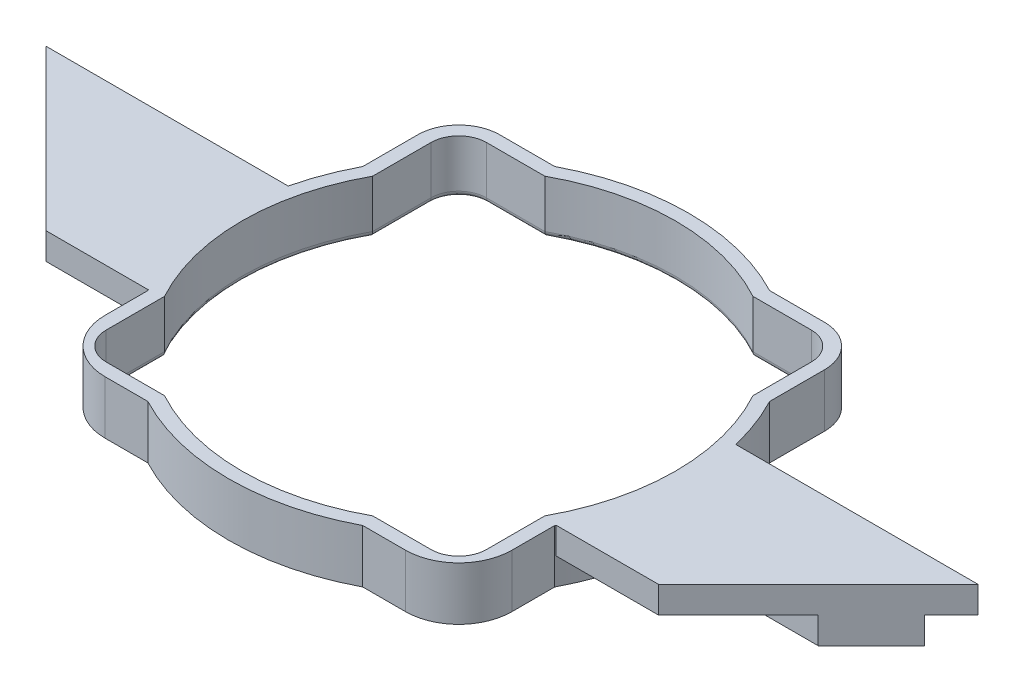
SolidWorks part; units mm, degrees
ref_plane "Front Plane" through (0, 0, 0) normal (0, 0, 1) x (1, 0, 0)
ref_plane "Top Plane" through (0, 0, 0) normal (0, 1, 0) x (1, 0, 0)
ref_plane "Right Plane" through (0, 0, 0) normal (1, 0, 0) x (0, 0, -1)
sketch "Sketch1" plane through (0, 0, 0) normal (0, 1, 0) x (1, 0, 0)
  line L1 (-127, -76.2) -> (127, -76.2)
  line L2 (-127, -76.2) -> (-127, 76.2)
  line L3 (-127, 76.2) -> (127, 76.2)
  line L4 (127, -76.2) -> (127, 76.2)
  line L5 (-127, -76.2) -> (127, 76.2) construction
  line L6 (-127, 76.2) -> (127, -76.2) construction
  point P0 (0, 0)
  dimension "D1" = 254
  dimension "D2" = 152.4
extrude "Boss-Extrude1" add sketch "Sketch1" along normal blind 12.7 contours L2 L3 L4 L1
sketch "Sketch4" plane through (0, 0, 0) normal (0, -1, 0) x (1, 0, 0)
  line L0 (45.339, 24.8219) -> (45.339, 38.735)
  line L1 (38.735, 45.339) -> (24.8219, 45.339)
  line L2 (-24.8219, 45.339) -> (-38.735, 45.339)
  line L3 (-45.339, 38.735) -> (-45.339, 24.8219)
  line L4 (-45.339, -24.8219) -> (-45.339, -38.735)
  line L5 (-38.735, -45.339) -> (-24.8219, -45.339)
  line L6 (24.8219, -45.339) -> (38.735, -45.339)
  line L7 (45.339, -38.735) -> (45.339, -24.8219)
  line L9 (45.085, 24.7569) -> (45.085, 38.735)
  line L10 (38.735, 45.085) -> (24.7569, 45.085)
  line L11 (-24.7569, 45.085) -> (-38.735, 45.085)
  line L12 (-45.085, 38.735) -> (-45.085, 24.7569)
  line L13 (-45.085, -24.7569) -> (-45.085, -38.735)
  line L14 (-38.735, -45.085) -> (-24.7569, -45.085)
  line L15 (24.7569, -45.085) -> (38.735, -45.085)
  line L24 (45.085, -38.735) -> (45.085, -24.7569)
  line L25 (45.085, 24.7569) -> (45.085, 38.735) construction
  line L26 (38.735, 45.085) -> (24.7569, 45.085) construction
  line L27 (-24.7569, 45.085) -> (-38.735, 45.085) construction
  line L28 (-45.085, 38.735) -> (-45.085, 24.7569) construction
  line L29 (-45.085, -24.7569) -> (-45.085, -38.735) construction
  line L30 (-38.735, -45.085) -> (-24.7569, -45.085) construction
  line L31 (24.7569, -45.085) -> (38.735, -45.085) construction
  line L32 (45.085, -38.735) -> (45.085, -24.7569) construction
  line L33 (48.514, 25.6213) -> (48.514, 38.735)
  line L34 (38.735, 48.514) -> (25.6213, 48.514)
  line L35 (-25.6213, 48.514) -> (-38.735, 48.514)
  line L36 (-48.514, 38.735) -> (-48.514, 25.6213)
  line L37 (-48.514, -25.6213) -> (-48.514, -38.735)
  line L38 (-38.735, -48.514) -> (-25.6213, -48.514)
  line L39 (25.6213, -48.514) -> (38.735, -48.514)
  line L40 (48.514, -38.735) -> (48.514, -25.6213)
  arc A0 (45.339, 38.735) -> (38.735, 45.339) centre (38.735, 38.735) ccw
  arc A1 (24.8219, 45.339) -> (-24.8219, 45.339) centre (0, 0) ccw
  arc A2 (-38.735, 45.339) -> (-45.339, 38.735) centre (-38.735, 38.735) ccw
  arc A3 (-45.339, 24.8219) -> (-45.339, -24.8219) centre (0, 0) ccw
  arc A4 (-45.339, -38.735) -> (-38.735, -45.339) centre (-38.735, -38.735) ccw
  arc A5 (-24.8219, -45.339) -> (24.8219, -45.339) centre (0, 0) ccw
  arc A6 (38.735, -45.339) -> (45.339, -38.735) centre (38.735, -38.735) ccw
  arc A7 (45.339, -24.8219) -> (45.339, 24.8219) centre (0, 0) ccw
  arc A24 (45.085, 38.735) -> (38.735, 45.085) centre (38.735, 38.735) ccw
  arc A25 (24.7569, 45.085) -> (-24.7569, 45.085) centre (0, 0) ccw
  arc A26 (-38.735, 45.085) -> (-45.085, 38.735) centre (-38.735, 38.735) ccw
  arc A27 (-45.085, 24.7569) -> (-45.085, -24.7569) centre (0, 0) ccw
  arc A28 (-45.085, -38.735) -> (-38.735, -45.085) centre (-38.735, -38.735) ccw
  arc A29 (-24.7569, -45.085) -> (24.7569, -45.085) centre (0, 0) ccw
  arc A30 (38.735, -45.085) -> (45.085, -38.735) centre (38.735, -38.735) ccw
  arc A31 (45.085, -24.7569) -> (45.085, 24.7569) centre (0, 0) ccw
  arc A32 (45.085, 38.735) -> (38.735, 45.085) centre (38.735, 38.735) ccw construction
  arc A33 (24.7569, 45.085) -> (-24.7569, 45.085) centre (0, 0) ccw construction
  arc A34 (-38.735, 45.085) -> (-45.085, 38.735) centre (-38.735, 38.735) ccw construction
  arc A35 (-45.085, 24.7569) -> (-45.085, -24.7569) centre (0, 0) ccw construction
  arc A36 (-45.085, -38.735) -> (-38.735, -45.085) centre (-38.735, -38.735) ccw construction
  arc A37 (-24.7569, -45.085) -> (24.7569, -45.085) centre (0, 0) ccw construction
  arc A38 (38.735, -45.085) -> (45.085, -38.735) centre (38.735, -38.735) ccw construction
  arc A39 (45.085, -24.7569) -> (45.085, 24.7569) centre (0, 0) ccw construction
  arc A40 (48.514, 38.735) -> (38.735, 48.514) centre (38.735, 38.735) ccw
  arc A41 (25.6213, 48.514) -> (-25.6213, 48.514) centre (0, 0) ccw
  arc A42 (-38.735, 48.514) -> (-48.514, 38.735) centre (-38.735, 38.735) ccw
  arc A43 (-48.514, 25.6213) -> (-48.514, -25.6213) centre (0, 0) ccw
  arc A44 (-48.514, -38.735) -> (-38.735, -48.514) centre (-38.735, -38.735) ccw
  arc A45 (-25.6213, -48.514) -> (25.6213, -48.514) centre (0, 0) ccw
  arc A46 (38.735, -48.514) -> (48.514, -38.735) centre (38.735, -38.735) ccw
  arc A47 (48.514, -25.6213) -> (48.514, 25.6213) centre (0, 0) ccw
  dimension "D1" = 0
  dimension "D2" = 0.254
  dimension "D3" = 3.175
extrude "Cut-Extrude1" cut sketch "Sketch4" against normal through all flip side to cut
sketch "Sketch5" plane through (0, 0, 0) normal (0, 1, 0) x (1, 0, 0)
  line L0 (54.4953, 6.35) -> (104.775, 6.35)
  line L1 (104.775, 6.35) -> (92.075, -6.35)
  line L2 (92.075, -6.35) -> (54.4953, -6.35)
  line L3 (0, 0) -> (0, 33.5108) construction
  line L4 (-92.075, -6.35) -> (-54.4953, -6.35)
  line L5 (-104.775, 6.35) -> (-92.075, -6.35)
  line L6 (-54.4953, 6.35) -> (-104.775, 6.35)
  arc A0 (48.514, -25.6213) -> (48.514, 25.6213) centre (0, 0) ccw construction
  arc A1 (54.4953, -6.35) -> (54.4953, 6.35) centre (0, 0) ccw
  arc A2 (-54.4953, -6.35) -> (-54.4953, 6.35) centre (0, 0) cw
  point P9 (98.425, 0)
  point P14 (115.1124, -6.35)
  point P15 (104.775, -6.35)
  point P16 (104.775, -6.35)
  point P17 (114.6569, -5.7905)
  point P20 (113.2371, 5.2793)
  dimension "D1" = 12.7
  dimension "D2" = 104.775
  dimension "D3" = 45
extrude "Boss-Extrude2" add sketch "Sketch5" along normal blind 6.35
sketch "Sketch6" plane through (0, 0, 0) normal (0, 1, 0) x (1, 0, 0)
  line L0 (53.3739, 12.7) -> (111.125, 12.7)
  line L1 (111.125, 12.7) -> (73.025, -25.4)
  line L2 (73.025, -25.4) -> (48.6302, -25.4)
  line L3 (92.075, -6.35) -> (104.775, 6.35) construction
  line L4 (104.775, 6.35) -> (54.4953, 6.35) construction
  line L5 (54.4953, -6.35) -> (92.075, -6.35) construction
  line L6 (0, 0) -> (0, 23.3719) construction
  line L7 (-73.025, -25.4) -> (-48.6302, -25.4)
  line L8 (-111.125, 12.7) -> (-73.025, -25.4)
  line L9 (-53.3739, 12.7) -> (-111.125, 12.7)
  arc A0 (48.514, -25.6213) -> (48.514, 25.6213) centre (0, 0) ccw construction
  arc A1 (48.6302, -25.4) -> (53.3739, 12.7) centre (0, 0) ccw
  arc A2 (-48.6302, -25.4) -> (-53.3739, 12.7) centre (0, 0) cw
  dimension "D1" = 6.35
  dimension "D2" = 19.05
extrude "Boss-Extrude3" add sketch "Sketch6" along normal blind 6.35 from surface starting at face at (76.5523, 6.35, 0)
fillet "Fillet1" radius 1.27 16 edges at (45.339, 0, 31.7785) (43.4047, 0, 43.4047) (-31.7785, 0, 45.339) (-43.4047, 0, 43.4047) (-45.339, 0, -31.7785) (-43.4047, 0, -43.4047) (45.339, 0, -31.7785) (43.4047, 0, -43.4047) (51.689, 0, 0) (31.7785, 0, 45.339) (0, 0, 51.689) (-45.339, 0, 31.7785) (-51.689, 0, 0) (-31.7785, 0, -45.339) (0, 0, -51.689) (31.7785, 0, -45.339)
sketch "Sketch9" plane through (0, 12.7, 0) normal (0, 1, 0) x (1, 0, 0)
  line L0 (48.514, -25.6213) -> (48.514, -38.735) construction
  line L1 (38.735, -48.514) -> (25.6213, -48.514) construction
  line L2 (0, 0) -> (0, -39.3727) construction
  line L3 (38.735, -48.514) -> (35.814, -48.514)
  line L4 (48.514, -35.814) -> (48.514, -38.735)
  line L5 (-48.514, -35.814) -> (-48.514, -38.735)
  line L6 (-38.735, -48.514) -> (-35.814, -48.514)
  arc A0 (35.814, -48.514) -> (48.514, -35.814) centre (35.814, -35.814) ccw
  arc A1 (38.735, -48.514) -> (48.514, -38.735) centre (38.735, -38.735) ccw construction
  arc A2 (38.735, -48.514) -> (48.514, -38.735) centre (38.735, -38.735) ccw
  arc A3 (-38.735, -48.514) -> (-48.514, -38.735) centre (-38.735, -38.735) cw
  arc A4 (-35.814, -48.514) -> (-48.514, -35.814) centre (-35.814, -35.814) cw
  dimension "D1" = 25.4
extrude "Cut-Extrude3" cut sketch "Sketch9" against normal through all
equation "\"tightTol\" = 0.005in"
equation "\"normTol\"= 0.01in"
equation "\"looseTol\"= 0.02in"
equation "\"D2@Sketch4\"=\"normTol\""
